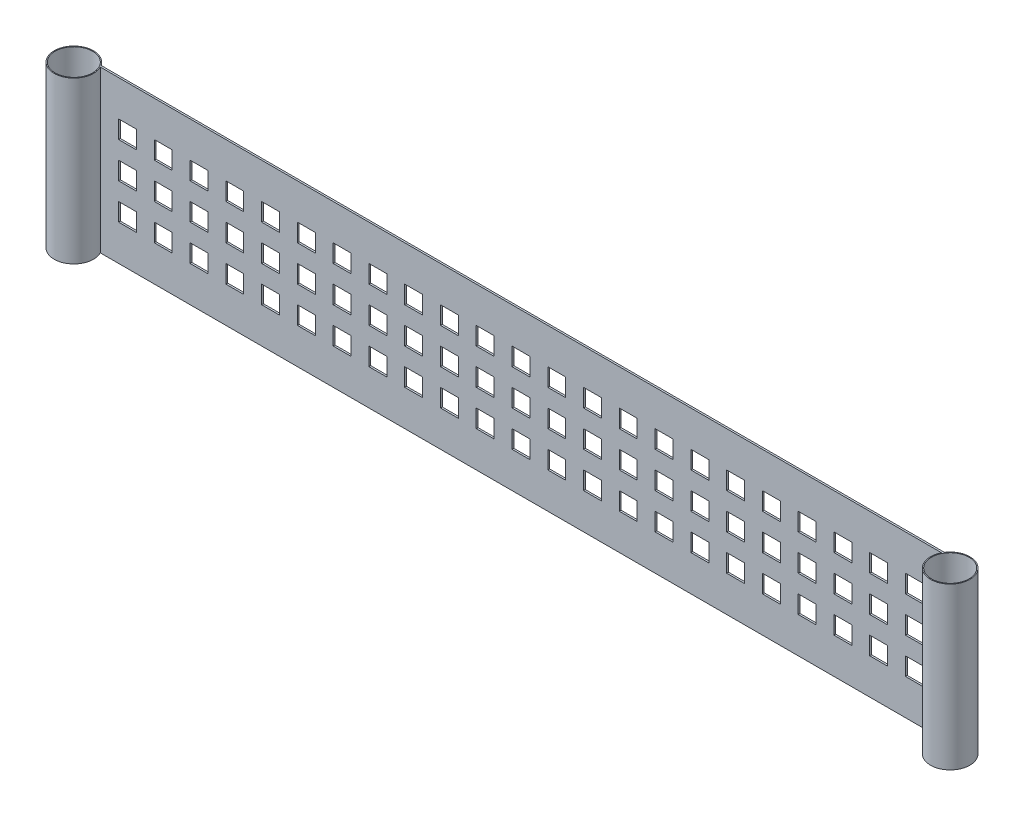
SolidWorks part; units mm, degrees
ref_plane "Front Plane" through (0, 0, 0) normal (0, 0, 1) x (1, 0, 0)
ref_plane "Top Plane" through (0, 0, 0) normal (0, 1, 0) x (1, 0, 0)
ref_plane "Right Plane" through (0, 0, 0) normal (1, 0, 0) x (0, 0, -1)
sketch "Sketch1" plane through (0, 0, 0) normal (0, 1, 0) x (1, 0, 0)
  line L0 (0, 0) -> (490, 0) construction
  line L1 (245, 3.3154) -> (245, 118.6617) construction
  line L2 (480.7805, 6) -> (9.2195, 6)
  line L3 (480.202, 5) -> (9.798, 5)
  arc A0 (9.2195, 6) -> (9.798, 5) centre (0, 0) ccw
  circle A1 centre (0, 0) radius 10.5
  circle A2 centre (490, 0) radius 10.5
  arc A3 (480.7805, 6) -> (480.202, 5) centre (490, 0) cw
  point P11 (9.2195, 6)
  point P12 (9.798, 5)
  point P13 (245, 5)
  point P15 (245, 6)
  dimension "D1" = 21
  dimension "D2" = 22
  dimension "D3" = 490
  dimension "D4" = 6
  dimension "D5" = 1
extrude "Boss-Extrude1" add sketch "Sketch1" along normal blind 90
ref_axis "Axis1" through (0, 90, 0) along (0, -1, 0)
sketch "Sketch2" plane through (0, 0, -5) normal (0, 0, 1) x (1, 0, 0)
  line L0 (9.798, 90) -> (480.202, 90) construction
  line L1 (20, 70) -> (30, 70)
  line L2 (20, 70) -> (20, 60)
  line L3 (20, 60) -> (30, 60)
  line L4 (30, 70) -> (30, 60)
  line L5 (0, 90) -> (0, 0) construction
  line L6 (50, 70) -> (50, 60)
  line L7 (40, 70) -> (50, 70)
  line L8 (40, 70) -> (40, 60)
  line L9 (40, 60) -> (50, 60)
  line L10 (70, 70) -> (70, 60)
  line L11 (60, 70) -> (70, 70)
  line L12 (60, 70) -> (60, 60)
  line L13 (60, 60) -> (70, 60)
  line L14 (90, 70) -> (90, 60)
  line L15 (80, 70) -> (90, 70)
  line L16 (80, 70) -> (80, 60)
  line L17 (80, 60) -> (90, 60)
  line L18 (110, 70) -> (110, 60)
  line L19 (100, 70) -> (110, 70)
  line L20 (100, 70) -> (100, 60)
  line L21 (100, 60) -> (110, 60)
  line L22 (130, 70) -> (130, 60)
  line L23 (120, 70) -> (130, 70)
  line L24 (120, 70) -> (120, 60)
  line L25 (120, 60) -> (130, 60)
  line L26 (150, 70) -> (150, 60)
  line L27 (140, 70) -> (150, 70)
  line L28 (140, 70) -> (140, 60)
  line L29 (140, 60) -> (150, 60)
  line L30 (170, 70) -> (170, 60)
  line L31 (160, 70) -> (170, 70)
  line L32 (160, 70) -> (160, 60)
  line L33 (160, 60) -> (170, 60)
  line L34 (190, 70) -> (190, 60)
  line L35 (180, 70) -> (190, 70)
  line L36 (180, 70) -> (180, 60)
  line L37 (180, 60) -> (190, 60)
  line L38 (210, 70) -> (210, 60)
  line L39 (200, 70) -> (210, 70)
  line L40 (200, 70) -> (200, 60)
  line L41 (200, 60) -> (210, 60)
  line L42 (230, 70) -> (230, 60)
  line L43 (220, 70) -> (230, 70)
  line L44 (220, 70) -> (220, 60)
  line L45 (220, 60) -> (230, 60)
  line L46 (250, 70) -> (250, 60)
  line L47 (240, 70) -> (250, 70)
  line L48 (240, 70) -> (240, 60)
  line L49 (240, 60) -> (250, 60)
  line L50 (270, 70) -> (270, 60)
  line L51 (260, 70) -> (270, 70)
  line L52 (260, 70) -> (260, 60)
  line L53 (260, 60) -> (270, 60)
  line L54 (290, 70) -> (290, 60)
  line L55 (280, 70) -> (290, 70)
  line L56 (280, 70) -> (280, 60)
  line L57 (280, 60) -> (290, 60)
  line L58 (310, 70) -> (310, 60)
  line L59 (300, 70) -> (310, 70)
  line L60 (300, 70) -> (300, 60)
  line L61 (300, 60) -> (310, 60)
  line L62 (330, 70) -> (330, 60)
  line L63 (320, 70) -> (330, 70)
  line L64 (320, 70) -> (320, 60)
  line L65 (320, 60) -> (330, 60)
  line L66 (350, 70) -> (350, 60)
  line L67 (340, 70) -> (350, 70)
  line L68 (340, 70) -> (340, 60)
  line L69 (340, 60) -> (350, 60)
  line L70 (370, 70) -> (370, 60)
  line L71 (360, 70) -> (370, 70)
  line L72 (360, 70) -> (360, 60)
  line L73 (360, 60) -> (370, 60)
  line L74 (390, 70) -> (390, 60)
  line L75 (380, 70) -> (390, 70)
  line L76 (380, 70) -> (380, 60)
  line L77 (380, 60) -> (390, 60)
  line L78 (410, 70) -> (410, 60)
  line L79 (400, 70) -> (410, 70)
  line L80 (400, 70) -> (400, 60)
  line L81 (400, 60) -> (410, 60)
  line L82 (430, 70) -> (430, 60)
  line L83 (420, 70) -> (430, 70)
  line L84 (420, 70) -> (420, 60)
  line L85 (420, 60) -> (430, 60)
  line L86 (450, 70) -> (450, 60)
  line L87 (440, 70) -> (450, 70)
  line L88 (440, 70) -> (440, 60)
  line L89 (440, 60) -> (450, 60)
  line L90 (470, 70) -> (470, 60)
  line L91 (460, 70) -> (470, 70)
  line L92 (460, 70) -> (460, 60)
  line L93 (460, 60) -> (470, 60)
  line L94 (50, 50) -> (50, 40)
  line L95 (40, 50) -> (50, 50)
  line L96 (40, 50) -> (40, 40)
  line L97 (40, 40) -> (50, 40)
  line L98 (70, 50) -> (70, 40)
  line L99 (60, 50) -> (70, 50)
  line L100 (60, 50) -> (60, 40)
  line L101 (60, 40) -> (70, 40)
  line L102 (90, 50) -> (90, 40)
  line L103 (80, 50) -> (90, 50)
  line L104 (80, 50) -> (80, 40)
  line L105 (80, 40) -> (90, 40)
  line L106 (110, 50) -> (110, 40)
  line L107 (100, 50) -> (110, 50)
  line L108 (100, 50) -> (100, 40)
  line L109 (100, 40) -> (110, 40)
  line L110 (130, 50) -> (130, 40)
  line L111 (120, 50) -> (130, 50)
  line L112 (120, 50) -> (120, 40)
  line L113 (120, 40) -> (130, 40)
  line L114 (150, 50) -> (150, 40)
  line L115 (140, 50) -> (150, 50)
  line L116 (140, 50) -> (140, 40)
  line L117 (140, 40) -> (150, 40)
  line L118 (170, 50) -> (170, 40)
  line L119 (160, 50) -> (170, 50)
  line L120 (160, 50) -> (160, 40)
  line L121 (160, 40) -> (170, 40)
  line L122 (190, 50) -> (190, 40)
  line L123 (180, 50) -> (190, 50)
  line L124 (180, 50) -> (180, 40)
  line L125 (180, 40) -> (190, 40)
  line L126 (210, 50) -> (210, 40)
  line L127 (200, 50) -> (210, 50)
  line L128 (200, 50) -> (200, 40)
  line L129 (200, 40) -> (210, 40)
  line L130 (230, 50) -> (230, 40)
  line L131 (220, 50) -> (230, 50)
  line L132 (220, 50) -> (220, 40)
  line L133 (220, 40) -> (230, 40)
  line L134 (250, 50) -> (250, 40)
  line L135 (240, 50) -> (250, 50)
  line L136 (240, 50) -> (240, 40)
  line L137 (240, 40) -> (250, 40)
  line L138 (270, 50) -> (270, 40)
  line L139 (260, 50) -> (270, 50)
  line L140 (260, 50) -> (260, 40)
  line L141 (260, 40) -> (270, 40)
  line L142 (290, 50) -> (290, 40)
  line L143 (280, 50) -> (290, 50)
  line L144 (280, 50) -> (280, 40)
  line L145 (280, 40) -> (290, 40)
  line L146 (310, 50) -> (310, 40)
  line L147 (300, 50) -> (310, 50)
  line L148 (300, 50) -> (300, 40)
  line L149 (300, 40) -> (310, 40)
  line L150 (330, 50) -> (330, 40)
  line L151 (320, 50) -> (330, 50)
  line L152 (320, 50) -> (320, 40)
  line L153 (320, 40) -> (330, 40)
  line L154 (350, 50) -> (350, 40)
  line L155 (340, 50) -> (350, 50)
  line L156 (340, 50) -> (340, 40)
  line L157 (340, 40) -> (350, 40)
  line L158 (370, 50) -> (370, 40)
  line L159 (360, 50) -> (370, 50)
  line L160 (360, 50) -> (360, 40)
  line L161 (360, 40) -> (370, 40)
  line L162 (390, 50) -> (390, 40)
  line L163 (380, 50) -> (390, 50)
  line L164 (380, 50) -> (380, 40)
  line L165 (380, 40) -> (390, 40)
  line L166 (410, 50) -> (410, 40)
  line L167 (400, 50) -> (410, 50)
  line L168 (400, 50) -> (400, 40)
  line L169 (400, 40) -> (410, 40)
  line L170 (430, 50) -> (430, 40)
  line L171 (420, 50) -> (430, 50)
  line L172 (420, 50) -> (420, 40)
  line L173 (420, 40) -> (430, 40)
  line L174 (450, 50) -> (450, 40)
  line L175 (440, 50) -> (450, 50)
  line L176 (440, 50) -> (440, 40)
  line L177 (440, 40) -> (450, 40)
  line L178 (470, 50) -> (470, 40)
  line L179 (460, 50) -> (470, 50)
  line L180 (460, 50) -> (460, 40)
  line L181 (460, 40) -> (470, 40)
  line L182 (50, 30) -> (50, 20)
  line L183 (40, 30) -> (50, 30)
  line L184 (40, 30) -> (40, 20)
  line L185 (40, 20) -> (50, 20)
  line L186 (70, 30) -> (70, 20)
  line L187 (60, 30) -> (70, 30)
  line L188 (60, 30) -> (60, 20)
  line L189 (60, 20) -> (70, 20)
  line L190 (90, 30) -> (90, 20)
  line L191 (80, 30) -> (90, 30)
  line L192 (80, 30) -> (80, 20)
  line L193 (80, 20) -> (90, 20)
  line L194 (110, 30) -> (110, 20)
  line L195 (100, 30) -> (110, 30)
  line L196 (100, 30) -> (100, 20)
  line L197 (100, 20) -> (110, 20)
  line L198 (130, 30) -> (130, 20)
  line L199 (120, 30) -> (130, 30)
  line L200 (120, 30) -> (120, 20)
  line L201 (120, 20) -> (130, 20)
  line L202 (150, 30) -> (150, 20)
  line L203 (140, 30) -> (150, 30)
  line L204 (140, 30) -> (140, 20)
  line L205 (140, 20) -> (150, 20)
  line L206 (170, 30) -> (170, 20)
  line L207 (160, 30) -> (170, 30)
  line L208 (160, 30) -> (160, 20)
  line L209 (160, 20) -> (170, 20)
  line L210 (190, 30) -> (190, 20)
  line L211 (180, 30) -> (190, 30)
  line L212 (180, 30) -> (180, 20)
  line L213 (180, 20) -> (190, 20)
  line L214 (210, 30) -> (210, 20)
  line L215 (200, 30) -> (210, 30)
  line L216 (200, 30) -> (200, 20)
  line L217 (200, 20) -> (210, 20)
  line L218 (230, 30) -> (230, 20)
  line L219 (220, 30) -> (230, 30)
  line L220 (220, 30) -> (220, 20)
  line L221 (220, 20) -> (230, 20)
  line L222 (250, 30) -> (250, 20)
  line L223 (240, 30) -> (250, 30)
  line L224 (240, 30) -> (240, 20)
  line L225 (240, 20) -> (250, 20)
  line L226 (270, 30) -> (270, 20)
  line L227 (260, 30) -> (270, 30)
  line L228 (260, 30) -> (260, 20)
  line L229 (260, 20) -> (270, 20)
  line L230 (290, 30) -> (290, 20)
  line L231 (280, 30) -> (290, 30)
  line L232 (280, 30) -> (280, 20)
  line L233 (280, 20) -> (290, 20)
  line L234 (310, 30) -> (310, 20)
  line L235 (300, 30) -> (310, 30)
  line L236 (300, 30) -> (300, 20)
  line L237 (300, 20) -> (310, 20)
  line L238 (330, 30) -> (330, 20)
  line L239 (320, 30) -> (330, 30)
  line L240 (320, 30) -> (320, 20)
  line L241 (320, 20) -> (330, 20)
  line L242 (350, 30) -> (350, 20)
  line L243 (340, 30) -> (350, 30)
  line L244 (340, 30) -> (340, 20)
  line L245 (340, 20) -> (350, 20)
  line L246 (370, 30) -> (370, 20)
  line L247 (360, 30) -> (370, 30)
  line L248 (360, 30) -> (360, 20)
  line L249 (360, 20) -> (370, 20)
  line L250 (390, 30) -> (390, 20)
  line L251 (380, 30) -> (390, 30)
  line L252 (380, 30) -> (380, 20)
  line L253 (380, 20) -> (390, 20)
  line L254 (410, 30) -> (410, 20)
  line L255 (400, 30) -> (410, 30)
  line L256 (400, 30) -> (400, 20)
  line L257 (400, 20) -> (410, 20)
  line L258 (430, 30) -> (430, 20)
  line L259 (420, 30) -> (430, 30)
  line L260 (420, 30) -> (420, 20)
  line L261 (420, 20) -> (430, 20)
  line L262 (450, 30) -> (450, 20)
  line L263 (440, 30) -> (450, 30)
  line L264 (440, 30) -> (440, 20)
  line L265 (440, 20) -> (450, 20)
  line L266 (470, 30) -> (470, 20)
  line L267 (460, 30) -> (470, 30)
  line L268 (460, 30) -> (460, 20)
  line L269 (460, 20) -> (470, 20)
  line L270 (30, 50) -> (30, 40)
  line L271 (20, 50) -> (30, 50)
  line L272 (20, 50) -> (20, 40)
  line L273 (20, 40) -> (30, 40)
  line L274 (30, 30) -> (30, 20)
  line L275 (20, 30) -> (30, 30)
  line L276 (20, 30) -> (20, 20)
  line L277 (20, 20) -> (30, 20)
  dimension "D1" = 10
  dimension "D2" = 20
  dimension "D3" = 20
  dimension "D4" = 23
  dimension "D5" = 3
extrude "Cut-Extrude1" cut sketch "Sketch2" against normal through all and the other way through all
